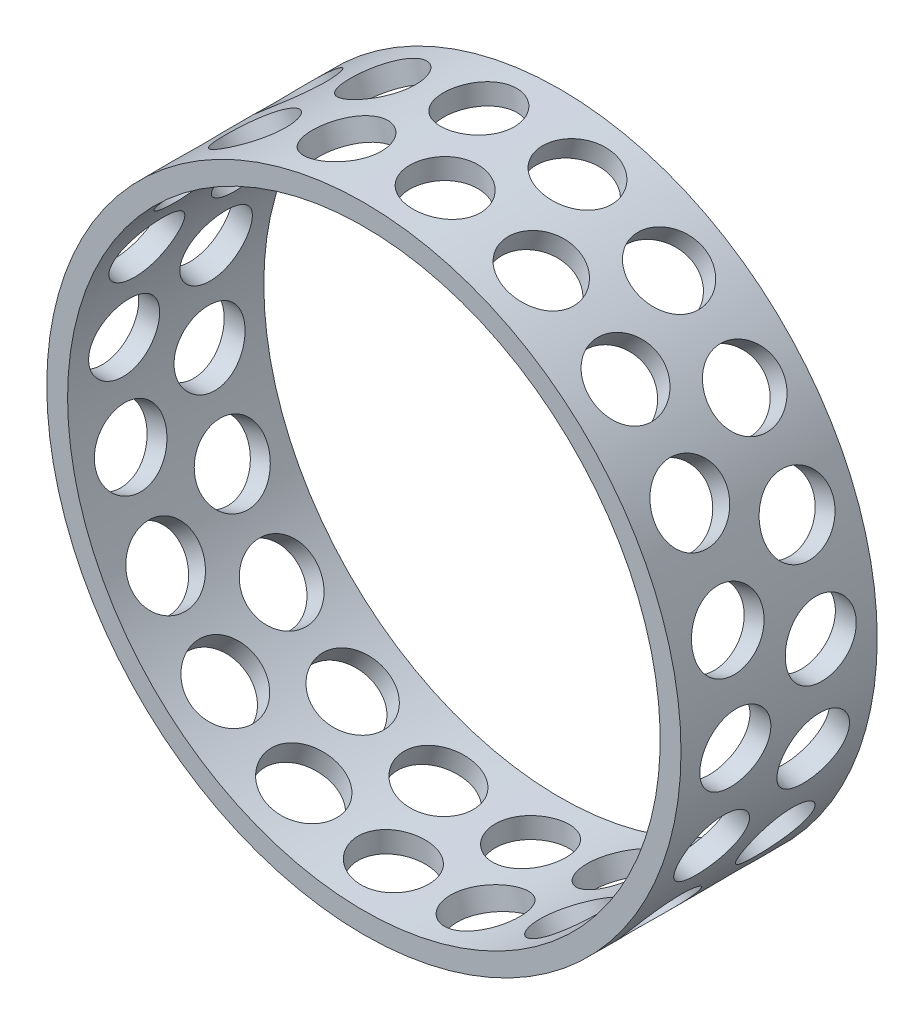
SolidWorks part; units mm, degrees
material "Plain Carbon Steel"
ref_plane "Front Plane" through (0, 0, 0) normal (0, 0, 1) x (1, 0, 0)
ref_plane "Top Plane" through (0, 0, 0) normal (0, 1, 0) x (1, 0, 0)
ref_plane "Right Plane" through (0, 0, 0) normal (1, 0, 0) x (0, 0, -1)
sketch "Sketch1" plane through (0, 0, 0) normal (1, 0, 0) x (0, 0, -1)
  line L0 (1, 76.2) -> (48.15, 76.2)
  line L1 (48.15, 76.2) -> (48.15, 71.2)
  line L2 (48.15, 71.2) -> (1, 71.2)
  line L3 (1, 71.2) -> (1, 76.2)
  dimension "D1" = 76.2
  dimension "D2" = 5
  dimension "D3" = 47.15
  dimension "D4" = 1
ref_axis "Axis1" through (0, 0, -50.5075) along (0, 0, 1)
revolve "Revolve1" add sketch "Sketch1" angle 360 about axis through (0, 0, -50.5075) along (0, 0, 1)
sketch "Sketch2" plane through (0, 0, 0) normal (1, 0, 0) x (0, 0, -1)
  line L0 (14.3098, 6.2149) -> (24.575, 0) construction
  line L1 (50.5075, 0) -> (-1.3575, 0) construction
  line L2 (24.575, 0) -> (34.8402, -6.2149) construction
  line L3 (1, 76.2) -> (1, -76.2) construction
  circle A0 centre (14.3098, 6.2149) radius 8.5
  circle A1 centre (34.8402, -6.2149) radius 8.5
  dimension "D1" = 17
  dimension "D2" = 12
  dimension "D3" = 23.575
extrude "Cut-Extrude1" cut sketch "Sketch2" against normal through all
pattern_circular "CirPattern1" count 20 over 360 about axis through (0, 0, -50.5075) along (0, 0, 1) of "Cut-Extrude1"
equation "\"TubeDiameter\" = 6.000in"
equation "\"D1@Sketch1\"=\"TubeDiameter\"/2"
